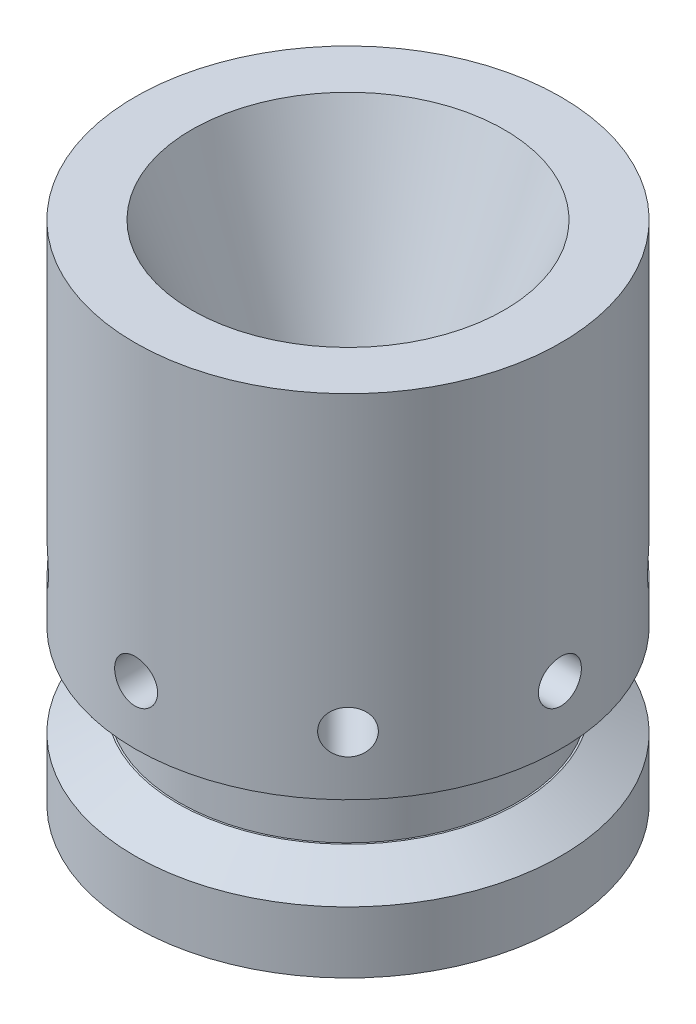
SolidWorks part; units mm, degrees
ref_plane "Front" through (0, 0, 0) normal (0, 0, 1) x (1, 0, 0)
ref_plane "Top" through (0, 0, 0) normal (0, 1, 0) x (1, 0, 0)
ref_plane "Right" through (0, 0, 0) normal (1, 0, 0) x (0, 0, -1)
sketch "Sketch2" plane through (0, 0, 0) normal (0, 0, 1) x (1, 0, 0)
  line L0 (0, 19.1415) -> (0, -24.752) construction
  line L1 (-15.8413, 0) -> (18.4815, 0) construction
  line L2 (-15.8413, 2) -> (18.4815, 2) construction
  line L3 (-2, 0) -> (-2, 2)
  line L4 (-10.9, 21.0703) -> (-10.9, -1) construction
  line L5 (-2, 0) -> (-10.9, -8.9)
  line L6 (-10.9, -8.9) -> (-10.9, -4.5)
  line L7 (-18.3668, 17) -> (19.9717, 17) construction
  line L8 (-2, 2) -> (-8, 17)
  line L9 (-8, 17) -> (-10.9, 17)
  line L10 (-10.9, 17) -> (-10.9, 2)
  line L11 (-10.9, -1) -> (-10.9, 2)
  line L12 (-10.9, -1) -> (-8.65, -1)
  line L14 (-10.9, -4.5) -> (-8.65, -4.5)
  line L15 (-8.65, -1) -> (-8.65, -4.5)
  line L16 (-10.9, -4.5) -> (-10.9, -24.752) construction
  dimension "D1" = 10.9
  dimension "D2" = 2
  dimension "D3" = 45
  dimension "D4" = 15
  dimension "D5" = 3.5
  dimension "ThrottleRadius" = 2
  dimension "NozzleRadius" = 8
  dimension "D6" = 2.25
  dimension "D7" = 1
revolve "Revolve1" add sketch "Sketch2" angle 360 about L0
ref_plane "Plane1" through (-10.9, 0, 0) normal (-1, 0, 0) x (0, 0, 1)
sketch "Sketch3" plane through (-10.9, 0, 0) normal (-1, 0, 0) x (0, 0, 1)
  line L0 (0, 17) -> (0, -8.4987) construction
  line L1 (8, 17) -> (-8, 17) construction
  line L2 (10.9, 17) -> (-10.9, 17) construction
  circle A0 centre (0, 2) radius 1.1
  dimension "D1" = 2.2
  dimension "D2" = 15
extrude "Cut-Extrude1" cut sketch "Sketch3" against normal blind 6
ref_axis "Axis1" through (0, 0, 0) along (0, 1, 0)
pattern_circular "CirPattern1" count 8 over 360 about axis through (0, 0, 0) along (0, 1, 0) of "Cut-Extrude1"
chamfer "Chamfer2" distance 1.25 angle 60 1 edges at (0, -4.5, 10.9) first distance on face at (0, -8.9, 10.9)
